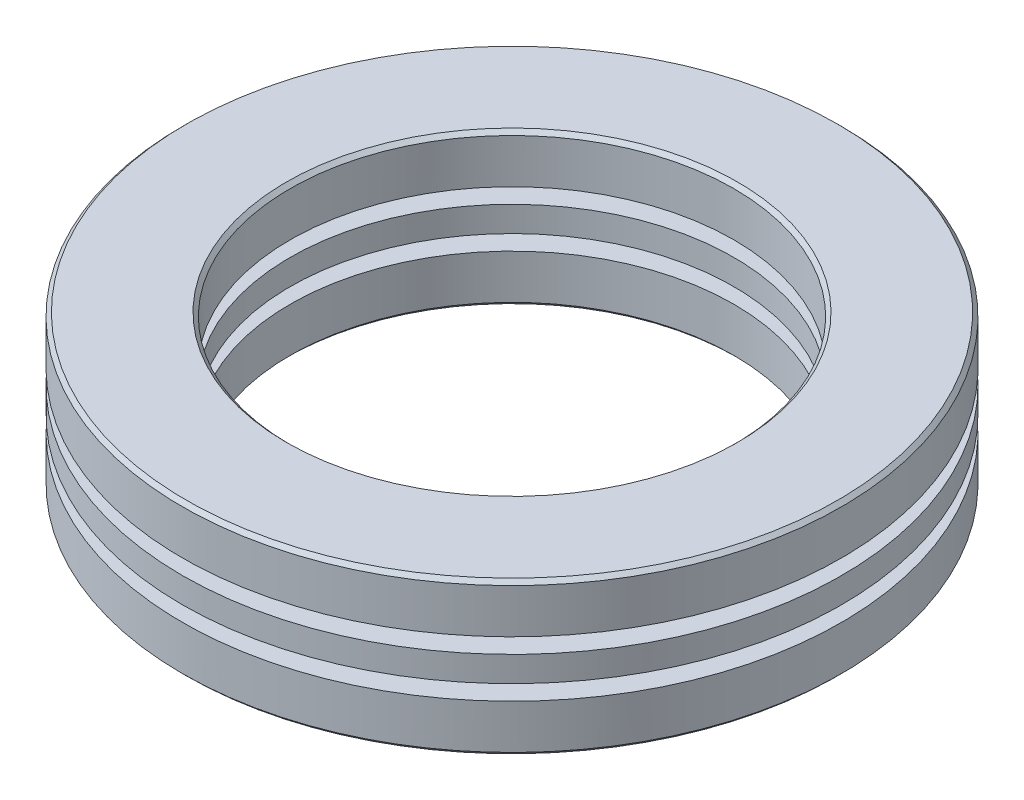
SolidWorks part; units mm, degrees
ref_plane "Front Plane" through (0, 0, 0) normal (0, 0, 1) x (1, 0, 0)
ref_plane "Top Plane" through (0, 0, 0) normal (0, 1, 0) x (1, 0, 0)
ref_plane "Right Plane" through (0, 0, 0) normal (1, 0, 0) x (0, 0, -1)
sketch "Sketch1" plane through (0, 0, 0) normal (0, 1, 0) x (1, 0, 0)
  circle A0 centre (0, 0) radius 17.5
  circle A1 centre (0, 0) radius 26
  dimension "D1" = 35
  dimension "D2" = 52
extrude "Boss-Extrude1" add sketch "Sketch1" along normal blind 3.8
ref_plane "Plane1" through (0, 5, 0) normal (0, 1, 0) x (1, 0, 0)
sketch "Sketch2" plane through (0, 5, 0) normal (0, 1, 0) x (1, 0, 0)
  circle A0 centre (0, 0) radius 17.5 construction
  circle A1 centre (0, 0) radius 26
  circle A2 centre (0, 0) radius 26
  circle A3 centre (0, 0) radius 17.5
  dimension "D1" = 0
extrude "Boss-Extrude2" add sketch "Sketch2" along normal blind 2 separate body
ref_plane "Plane2" through (0, 8.2, 0) normal (0, 1, 0) x (1, 0, 0)
sketch "Sketch3" plane through (0, 8.2, 0) normal (0, 1, 0) x (1, 0, 0)
  circle A0 centre (0, 0) radius 17.5 construction
  circle A1 centre (0, 0) radius 26
  circle A2 centre (0, 0) radius 26
  circle A3 centre (0, 0) radius 17.5
  dimension "D1" = 0
extrude "Boss-Extrude3" add sketch "Sketch3" along normal blind 3.8 separate body
sketch "Sketch4" plane through (0, 0, 0) normal (0, 0, 1) x (1, 0, 0)
  line L0 (-23.95, 6) -> (-19.55, 6)
  arc A0 (-19.55, 6) -> (-23.95, 6) centre (-21.75, 6) ccw
  dimension "D3" = 4.4
  dimension "D1" = 6
  dimension "D2" = 21.75
revolve "Cut-Revolve1" cut sketch "Sketch4" angle 360 about L0
revolve "Revolve1" add sketch "Sketch4<2>" angle 360 about L0
sketch "Sketch4<2>" plane through (0, 0, 0) normal (0, 0, 1) x (1, 0, 0) same geometry as "Sketch4"
pattern_circular "CirPattern2" count 16 over 360 about axis through (0, 12, 0) along (0, -1, 0) of "Cut-Revolve1" reverse direction yes
pattern_circular "CirPattern3" count 16 over 360 about axis through (0, 12, 0) along (0, -1, 0) of bodies 105
chamfer "Chamfer1" distance 0.3 angle 45 2 edges at (0, 12, 17.5) (0, 12, 26)
chamfer "Chamfer2" distance 0.3 angle 45 2 edges at (0, 0, 17.5) (0, 0, 26)
